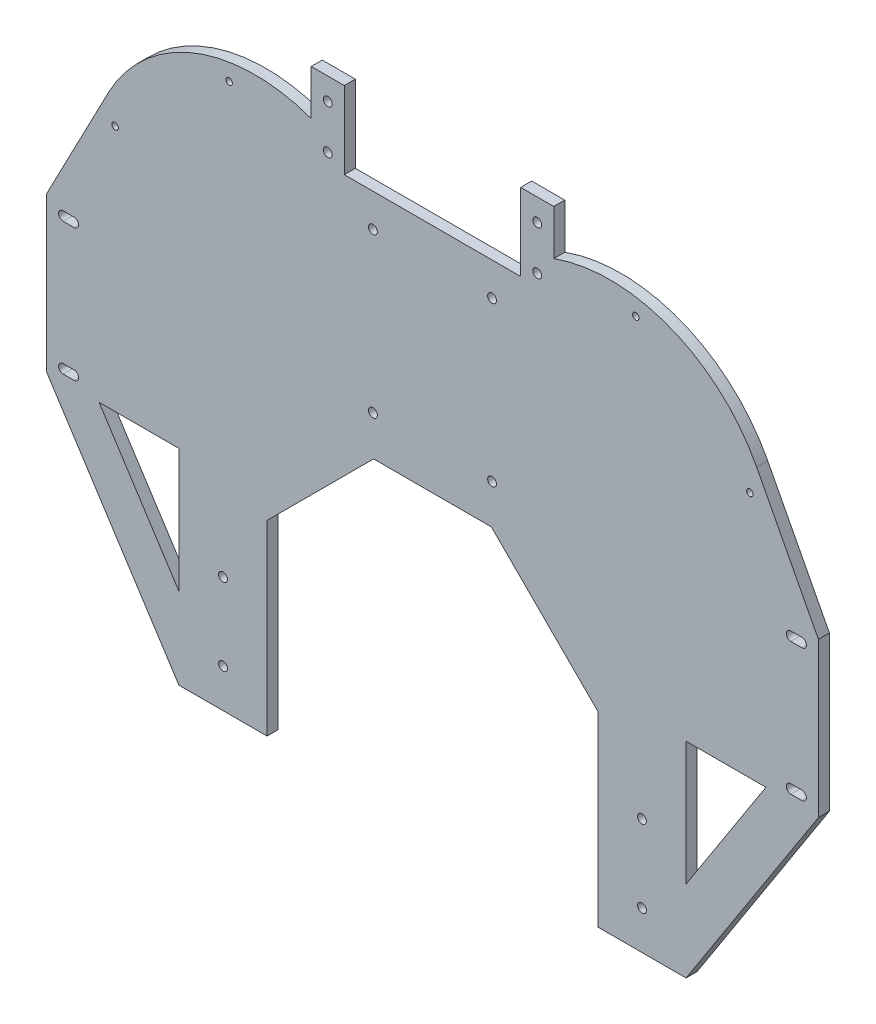
SolidWorks part; units mm, degrees
ref_plane "Front Plane" through (0, 0, 0) normal (0, 0, 1) x (1, 0, 0)
ref_plane "Top Plane" through (0, 0, 0) normal (0, 1, 0) x (1, 0, 0)
ref_plane "Right Plane" through (0, 0, 0) normal (1, 0, 0) x (0, 0, -1)
sketch "Sketch1" plane through (0, 0, 0) normal (0, 0, 1) x (1, 0, 0)
  line L1 (-100, -75) -> (100, -75)
  line L2 (-100, -75) -> (-100, 75)
  line L3 (-100, 75) -> (100, 75)
  line L4 (100, -75) -> (100, 75)
  line L5 (-100, -75) -> (100, 75) construction
  line L6 (-100, 75) -> (100, -75) construction
  line L8 (-47.5, 40) -> (47.5, 40) construction
  line L9 (0, 75) -> (0, -75) construction
  line L10 (-27, -52) -> (27, -52) construction
  line L11 (-27, -52) -> (-27, 20) construction
  line L12 (-27, 20) -> (27, 20) construction
  line L13 (27, -52) -> (27, 20) construction
  line L14 (-27, -52) -> (27, 20) construction
  line L15 (-27, 20) -> (27, -52) construction
  line L23 (-55, 70) -> (55, 70)
  line L24 (-55, 70) -> (-55, -70)
  line L25 (-55, -70) -> (55, -70)
  line L26 (55, 70) -> (55, -70)
  line L27 (-55, 70) -> (55, -70) construction
  line L28 (-55, -70) -> (55, 70) construction
  line L29 (-40, 70) -> (40, 70)
  line L30 (-40, 70) -> (-40, 35)
  line L31 (-40, 35) -> (40, 35)
  line L32 (40, 70) -> (40, 35)
  line L33 (-40, 70) -> (40, 35) construction
  line L34 (-40, 35) -> (40, 70) construction
  circle A2 centre (-47.5, 40) radius 2
  circle A3 centre (47.5, 40) radius 2
  circle A4 centre (-27, 20) radius 2
  circle A5 centre (27, 20) radius 2
  circle A6 centre (27, -52) radius 2
  circle A7 centre (-27, -52) radius 2
  circle A8 centre (-47.5, 60) radius 2
  circle A9 centre (47.5, 60) radius 2
  point P0 (0, 0)
  point P15 (0, 40)
  point P18 (0, -16)
  point P56 (0, 0)
  point P63 (0, 52.5)
  dimension "D3" = 4
  dimension "D4" = 20
  dimension "D5" = 4
  dimension "D8" = 4
  dimension "D1" = 150
  dimension "D2" = 200
  dimension "D6" = 72
  dimension "D7" = 54
  dimension "D14" = 30
  dimension "D15" = 140
  dimension "D16" = 110
  dimension "D17" = 95
  dimension "D18" = 20
  dimension "D19" = 35
  dimension "D20" = 80
extrude "Boss-Extrude1" add sketch "Sketch1" along normal blind 5 contours L23 L32 L31 L30 L24 L25 L26 A7 A6 A5 A4 A3 A2 region at (0, -11.8972, 0)
sketch "Sketch2" plane through (0, 0, 0) normal (0, 0, 1) x (1, 0, 0)
  line L0 (-55, -70) -> (-100.8579, -115.8579) construction
  line L1 (-55, 70) -> (-55, -70) construction
  line L2 (-55, -41.7157) -> (-115, -101.7157)
  line L3 (-26.7157, -70) -> (-86.7157, -130)
  line L4 (-55, -70) -> (55, -70) construction
  line L5 (-115, -101.7157) -> (-86.7157, -130)
  line L6 (-115, -101.7157) -> (-115, -203)
  line L7 (-75, -118.2843) -> (-75, -203)
  line L8 (-75, -203) -> (-115, -203)
  line L9 (0, 75) -> (0, -75) construction
  line L10 (-55, -41.7157) -> (-26.7157, -70)
  line L11 (-55, 70) -> (-55, -70) construction
  line L12 (-75, -203) -> (-115, -203) construction
  line L13 (-55, -70) -> (55, -70) construction
  line L14 (-55, 70) -> (-55, -70) construction
  circle A0 centre (-95, -150.5) radius 2
  circle A1 centre (-95, -185.5) radius 2
  dimension "D5" = 4
  dimension "D6" = 4
  dimension "D1" = 135
  dimension "D2" = 40
  dimension "D3" = 40
  dimension "D4" = 75
extrude "Boss-Extrude2" add sketch "Sketch2" along normal blind 5 contours L8 L7 L3 L5 L6 | L10 L2 L5 L3 region at (-70.8579, -85.8579, 0) region at (-95.9289, -160.2024, 0)
mirror "Mirror1" about plane through (0, 0, 0) normal (1, 0, 0) of "Boss-Extrude2"
sketch "Sketch3" plane through (0, 0, 5) normal (0, 0, 1) x (1, 0, 0)
  line L0 (0, 0) -> (0, 95.843) construction
  line L1 (-80.5, -21) -> (-92.2213, 45.4745) construction
  line L2 (-80.5, -21) -> (-143.9293, 2.0864) construction
  line L3 (-80.5, -21) -> (-148, -21) construction
  line L4 (-42.1979, -85.4821) -> (-26.7157, -70)
  line L5 (-26.7157, -70) -> (-23.7197, -70)
  line L6 (-26.7157, -70) -> (26.7157, -70) construction
  line L7 (-26.7157, -70) -> (-75, -118.2843) construction
  line L8 (26.7157, -70) -> (23.7197, -70)
  line L9 (42.1979, -85.4821) -> (26.7157, -70)
  circle A0 centre (-80.5, -21) radius 60 construction
  circle A1 centre (-80.5, -21) radius 75
  circle A2 centre (-80.5, -21) radius 67.5 construction
  circle A3 centre (-92.2213, 45.4745) radius 1.4732
  circle A4 centre (-143.9293, 2.0864) radius 1.4732
  circle A5 centre (-47.5, 40) radius 2 construction
  circle A6 centre (143.9293, 2.0864) radius 1.4732
  circle A7 centre (92.2213, 45.4745) radius 1.4732
  circle A8 centre (80.5, -21) radius 75
  circle A9 centre (-47.5, 40) radius 2
  circle A10 centre (-27, 20) radius 2
  circle A11 centre (-27, -52) radius 2
  circle A12 centre (-27, 20) radius 2 construction
  circle A13 centre (-27, -52) radius 2 construction
  circle A14 centre (47.5, 40) radius 2
  circle A15 centre (27, 20) radius 2
  circle A16 centre (27, -52) radius 2
  line M5 (-26.7157, -70) -> (26.7157, -70)
  line M6 (26.7157, -70) -> (75, -118.2843)
  line M10 (115, -101.7157) -> (55, -41.7157)
  line M11 (55, -41.7157) -> (55, 70)
  line M13 (40, 70) -> (40, 35)
  line M14 (40, 35) -> (-40, 35)
  line M15 (-40, 35) -> (-40, 70)
  line M17 (-55, 70) -> (-55, -41.7157)
  line M18 (-55, -41.7157) -> (-115, -101.7157)
  line M22 (-75, -118.2843) -> (-26.7157, -70)
  circle M23 centre (-47.5, 40) radius 2
  circle M24 centre (47.5, 40) radius 2
  circle M25 centre (-27, 20) radius 2
  circle M26 centre (27, 20) radius 2
  circle M27 centre (27, -52) radius 2
  circle M28 centre (-27, -52) radius 2
  dimension "D1" = 120
  dimension "D3" = 7.5
  dimension "D4" = 61
  dimension "D8" = 2.9464
  dimension "D5" = 80
  dimension "D6" = 20
  dimension "D7" = 161
  dimension "D2" = 15
extrude "Boss-Extrude3" add sketch "Sketch3" against normal up to surface (5 mm away) contours A1 A4 A3 M17 M18 | A1 M15 M17 M18 M22 M5 M14 M28 M25 M23 | A8 M10 M11 M13 M14 M5 M6 M27 M26 M24 | A8 A6 A7 M11 M10 region at (-42.8459, -33.3688, 5) region at (-102.3675, -14.0811, 5) region at (42.8459, -33.3688, 5) region at (102.3675, -14.0811, 5) up to face at (0, -62.524, 0)
sketch "Sketch4" plane through (0, 0, 5) normal (0, 0, 1) x (1, 0, 0)
  line L0 (-175, -110) -> (-115, -203)
  line L1 (-100, -110) -> (-115, -110) construction
  line L2 (-100, -110) -> (-100, -40)
  line L3 (-100, -40) -> (-152.4428, -40)
  line L4 (-175, -110) -> (-175, -40)
  line L5 (-100, -110) -> (-175, -40) construction
  line L6 (-100, -40) -> (-175, -110) construction
  line L7 (-151.1989, -110) -> (-115, -166.1083)
  line L8 (-115, -101.7157) -> (-115, -203) construction
  line L9 (-115, -166.1083) -> (-115, -203)
  line L10 (-151.1989, -110) -> (-175, -110) construction
  line L11 (-175, -40) -> (-146.9976, 13.6853)
  line L12 (-152.4428, -40) -> (-152.8464, -40.7738)
  line L13 (-152.4428, -40) -> (-175, -40) construction
  line L14 (-175, -75) -> (-100, -75) construction
  line L15 (-165, -40) -> (-165, -75) construction
  line L16 (-115, -110) -> (-151.1989, -110)
  line L18 (-100, -110) -> (-100, -101.7157)
  line L19 (-100, -101.7157) -> (-115, -101.7157)
  line L20 (-115, -110) -> (-115, -101.7157)
  line L21 (-100, -110) -> (-115, -101.7157) construction
  line L22 (-100, -101.7157) -> (-115, -110) construction
  line L23 (-162.5, -45) -> (-167.5, -45) construction
  line L24 (-162.5, -47.05) -> (-167.5, -47.05)
  line L25 (-162.5, -42.95) -> (-167.5, -42.95)
  line L26 (-162.5, -105) -> (-167.5, -105) construction
  line L27 (-162.5, -102.95) -> (-167.5, -102.95)
  line L28 (-162.5, -107.05) -> (-167.5, -107.05)
  circle A0 centre (-143.9293, 2.0864) radius 1.4732
  circle A1 centre (-143.9293, 2.0864) radius 1.4732 construction
  arc A2 (-55, 49.5319) -> (-105.1261, -91.8418) centre (-80.5, -21) ccw construction
  arc A3 (-152.8464, -40.7738) -> (-146.9976, 13.6853) centre (-80.5, -21) cw
  circle A4 centre (-165, -45) radius 2.05 construction
  circle A6 centre (-165, -105) radius 2.05 construction
  arc A7 (-162.5, -47.05) -> (-162.5, -42.95) centre (-162.5, -45) ccw
  arc A8 (-167.5, -42.95) -> (-167.5, -47.05) centre (-167.5, -45) ccw
  arc A9 (-162.5, -102.95) -> (-162.5, -107.05) centre (-162.5, -105) cw
  arc A10 (-167.5, -107.05) -> (-167.5, -102.95) centre (-167.5, -105) cw
  point P0 (-137.5, -75)
  point P31 (-164.4904, -54.9613)
  point P36 (-107.5, -105.8579)
  point P38 (-165, -45)
  point P48 (-165, -105)
  arc M14 (-55, 49.5319) -> (-105.1261, -91.8418) centre (-80.5, -21) ccw
  line M15 (-105.1261, -91.8418) -> (-115, -101.7157)
  line M16 (-115, -101.7157) -> (-115, -203)
  dimension "D7" = 4.1
  dimension "D9" = 2.05
  dimension "D1" = 100
  dimension "D2" = 40
  dimension "D3" = 75
  dimension "D4" = 70
  dimension "D5" = 20
  dimension "D6" = 20
  dimension "D8" = 10
  dimension "D10" = 5
  dimension "D11" = 5
extrude "Boss-Extrude4" add sketch "Sketch4" against normal up to surface (5 mm away) contours L16 L11 L4 L0 L7 A8 L25 A7 L24 L28 A10 L27 A9 M16 M15 M14 region at (-147.1729, -100.1234, 5) up to face at (0, -53.8091, 0)
mirror "Mirror2" about plane through (0, 0, 0) normal (1, 0, 0) of "Boss-Extrude4"
